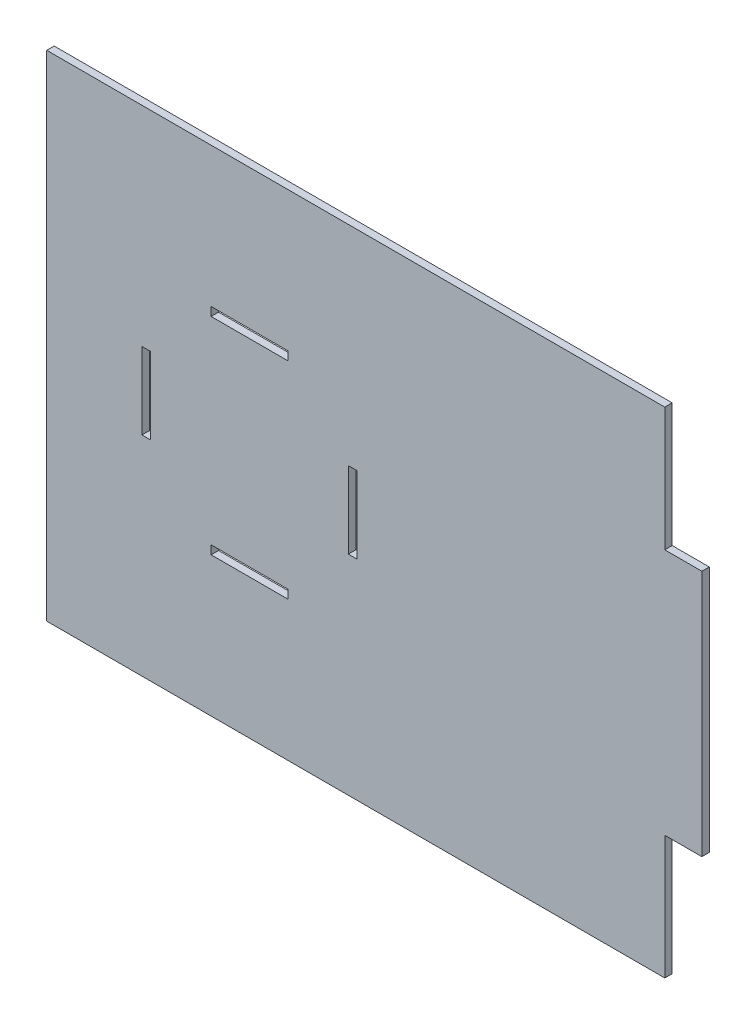
SolidWorks part; units mm, degrees
ref_plane "Plano frontal" through (0, 0, 0) normal (0, 0, 1) x (1, 0, 0)
ref_plane "Plano superior" through (0, 0, 0) normal (0, 1, 0) x (1, 0, 0)
ref_plane "Plano direito" through (0, 0, 0) normal (1, 0, 0) x (0, 0, -1)
sketch "Esboço1" plane through (0, 0, 0) normal (0, 0, 1) x (1, 0, 0)
  line L1 (-250, -100) -> (250, -100)
  line L2 (-250, -100) -> (-250, 100)
  line L3 (-250, 100) -> (250, 100)
  line L4 (250, -100) -> (250, 100)
  line L5 (-250, -100) -> (250, 100) construction
  line L6 (-250, 100) -> (250, -100) construction
  point P0 (0, 0)
  dimension "D1" = 500
  dimension "D2" = 200
extrude "Ressalto-extrusão1" add sketch "Esboço1" along normal blind 3
sketch "Esboço2" plane through (0, 0, 3) normal (0, 0, 1) x (1, 0, 0)
  line L0 (-250, 0) -> (250, 0) construction
  line L1 (-250, 100) -> (-250, -100) construction
  line L2 (250, -100) -> (250, 100) construction
  line L3 (0, 100) -> (0, -100) construction
  line L4 (250, 100) -> (-250, 100) construction
  line L5 (-250, -100) -> (250, -100) construction
  line L6 (-168, 100) -> (-168, -100) construction
  line L11 (211.5, 15.5) -> (208, 15.5)
  line L12 (208, -15.5) -> (208, 15.5)
  line L13 (-128, -15.5) -> (-124.5, -15.5)
  line L14 (-128, -15.5) -> (-128, 15.5)
  line L15 (-128, 15.5) -> (-124.5, 15.5)
  line L16 (-124.5, -15.5) -> (-124.5, 15.5)
  line L17 (-128, -15.5) -> (-124.5, 15.5) construction
  line L18 (-128, 15.5) -> (-124.5, -15.5) construction
  line L19 (-211.5, -15.5) -> (-208, -15.5)
  line L20 (-211.5, -15.5) -> (-211.5, 15.5)
  line L21 (-211.5, 15.5) -> (-208, 15.5)
  line L22 (-208, -15.5) -> (-208, 15.5)
  line L23 (-211.5, -15.5) -> (-208, 15.5) construction
  line L24 (-211.5, 15.5) -> (-208, -15.5) construction
  line L25 (-183.5, 40) -> (-152.5, 40)
  line L26 (-183.5, -43.5) -> (-152.5, -43.5)
  line L27 (-183.5, -43.5) -> (-183.5, -40)
  line L28 (-183.5, -40) -> (-152.5, -40)
  line L29 (-152.5, -43.5) -> (-152.5, -40)
  line L30 (-183.5, -43.5) -> (-152.5, -40) construction
  line L31 (-183.5, -40) -> (-152.5, -43.5) construction
  line L32 (-152.5, 43.5) -> (-152.5, 40)
  line L33 (-183.5, 43.5) -> (-152.5, 43.5)
  line L34 (-183.5, 43.5) -> (-183.5, 40)
  line L35 (211.5, -15.5) -> (208, -15.5)
  line L36 (211.5, -15.5) -> (211.5, 15.5)
  line L37 (128, 15.5) -> (124.5, 15.5)
  line L38 (124.5, -15.5) -> (124.5, 15.5)
  line L39 (128, -15.5) -> (124.5, -15.5)
  line L40 (128, -15.5) -> (128, 15.5)
  line L41 (183.5, -40) -> (152.5, -40)
  line L42 (152.5, -43.5) -> (152.5, -40)
  line L43 (183.5, -43.5) -> (152.5, -43.5)
  line L44 (183.5, -43.5) -> (183.5, -40)
  line L45 (183.5, 43.5) -> (183.5, 40)
  line L46 (183.5, 43.5) -> (152.5, 43.5)
  line L47 (152.5, 43.5) -> (152.5, 40)
  line L48 (183.5, 40) -> (152.5, 40)
  point P17 (-126.25, 0)
  point P22 (-209.75, 0)
  point P29 (-168, -41.75)
  dimension "D3" = 3.5
  dimension "D4" = 31
  dimension "D6" = 122
  dimension "D7" = 31
  dimension "D8" = 3.5
  dimension "D9" = 80
  dimension "D10" = 31
  dimension "D11" = 3.5
  dimension "D12" = 80
  dimension "D13" = 40
extrude "Corte-extrusão1" cut sketch "Esboço2" against normal through all
sketch "Esboço3" plane through (0, 0, 3) normal (0, 0, 1) x (1, 0, 0)
  line L0 (0, 100) -> (0, 50)
  line L1 (250, 100) -> (-250, 100) construction
  line L2 (-250, -100) -> (250, -100) construction
  line L3 (0, -50) -> (15, -50)
  line L4 (15, -50) -> (15, 50)
  line L5 (15, 50) -> (0, 50)
  line L6 (0, -50) -> (0, -100)
  line L11 (250, -100) -> (250, 100)
  line L12 (250, 100) -> (-250, 100)
  line L13 (-250, 100) -> (-250, -100)
  line L14 (-250, -100) -> (250, -100)
  line L15 (250, -100) -> (250, 100)
  line L16 (250, 100) -> (0, 100)
  line L18 (0, -100) -> (250, -100)
  dimension "D1" = 100
  dimension "D2" = 15
  dimension "D3" = 50
  dimension "D4" = 0
extrude "Corte-extrusão2" cut sketch "Esboço3" against normal through all
